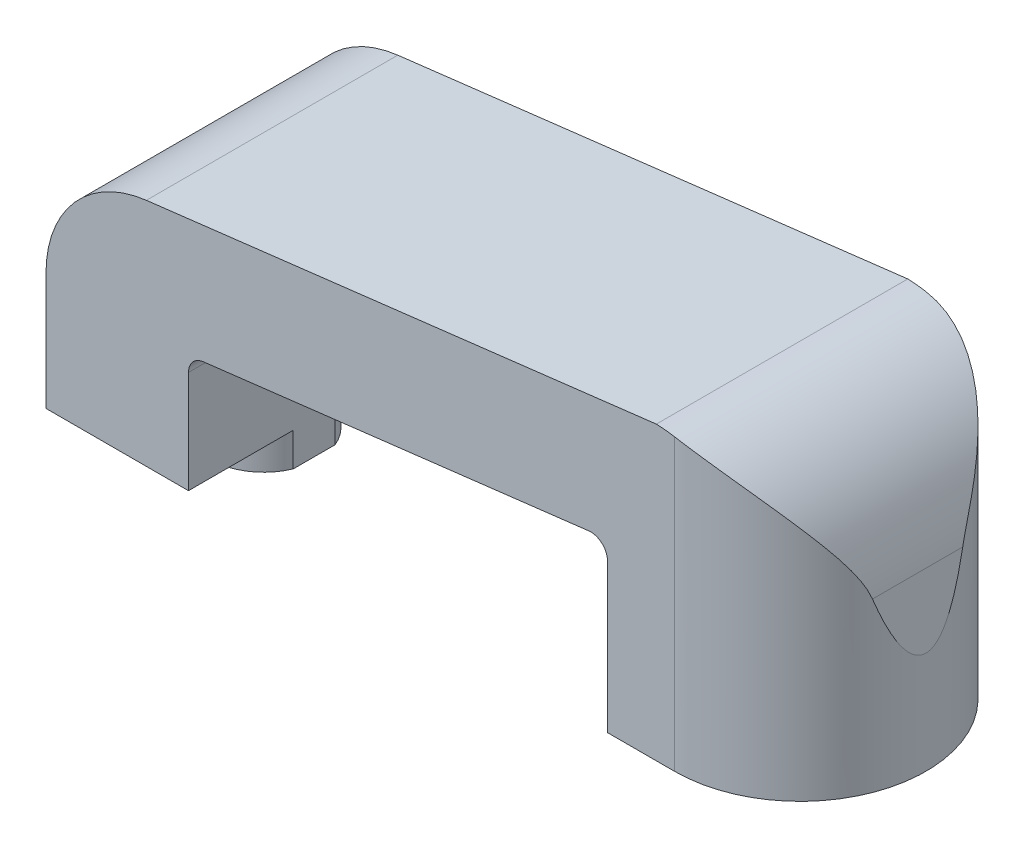
SolidWorks part; units mm, degrees
ref_plane "Ön Düzlem" through (0, 0, 0) normal (0, 0, 1) x (1, 0, 0)
ref_plane "Üst Düzlem" through (0, 0, 0) normal (0, 1, 0) x (1, 0, 0)
ref_plane "Sağ Düzlem" through (0, 0, 0) normal (1, 0, 0) x (0, 0, -1)
sketch "Sketch3" plane through (0, 0, 0) normal (0, 0, 1) x (1, 0, 0)
  line L0 (31.7681, 33.5206) -> (31.7681, 0) construction
  line L1 (0, 0) -> (-8.5, 0)
  line L2 (0, 0) -> (0, 6.1128)
  line L3 (0, 7) -> (-8.5, 7)
  line L4 (-8.5, 0) -> (-8.5, 7)
  line L5 (0.8809, 7.1057) -> (23.8809, 9.8657)
  line L6 (25, 0) -> (36, 0)
  line L7 (25, 0) -> (25, 8.8728)
  line L8 (25, 10) -> (36, 10)
  line L9 (36, 0) -> (36, 10)
  line L10 (-8.5, 0) -> (41.9166, 0) construction
  line L11 (-2.5127, 13.7487) -> (27.9143, 17.3999)
  arc A0 (-2.5127, 13.7487) -> (-8.5, 7) centre (-1.7029, 7) ccw
  arc A1 (27.9143, 17.3999) -> (36, 10) centre (27.5799, 8.9171) cw
  arc A2 (23.8809, 9.8657) -> (25, 8.8728) centre (24, 8.8728) cw
  arc A3 (0.8809, 7.1057) -> (0, 6.1128) centre (1, 6.1128) ccw
  point P15 (27.0903, 16.0845)
  point P17 (24.5808, 15.9874)
  point P18 (24.5808, 15.9874)
  point P25 (24.5808, 15.9874)
  point P26 (24.5808, 15.9874)
  point P27 (24.5808, 15.9874)
  point P28 (29.5444, 16.1291)
  point P29 (25, 17.08)
  dimension "D7" = 1
  dimension "D1" = 8.5
  dimension "D2" = 11
  dimension "D3" = 25
  dimension "D4" = 7
  dimension "D5" = 10
  dimension "D6" = 7
extrude "Boss-Extrude2" add sketch "Sketch3" along normal blind 15 contours A3 L5 A2 L7 L6 L9 A1 L11 A0 L4 L1 L2 region at (15.4185, 9.2084, 0)
sketch "Sketch4" plane through (0, 0, 0) normal (0, -1, 0) x (1, 0, 0)
  line L0 (25, 15) -> (25, 0) construction
  line L1 (29, 7.5) -> (29, 17.5654) construction
  line L2 (29, 7.5) -> (29, -2.3263) construction
  line L3 (25, 15) -> (36, 15) construction
  line L4 (25, 0) -> (36, 0) construction
  line L5 (36, 15) -> (36, 0) construction
  line L6 (29, 15) -> (36, 15)
  line L7 (29, 15) -> (29, 0)
  line L8 (29, 0) -> (36, 0)
  line L10 (36, 15) -> (36, 0)
  circle A0 centre (29, 7.5) radius 1.8409
  arc A1 (29, 15) -> (29, 0) centre (29, 7.5) cw
  point P5 (29, 15)
  point P6 (29, 0)
  line M5 (25, 0) -> (36, 0)
  line M6 (36, 0) -> (36, 15)
  line M7 (36, 15) -> (25, 15)
  dimension "D1" = 4
extrude "Cut-Extrude1" cut sketch "Sketch4" against normal blind 25 contours A1 M7 M6 | A1 M6 M5 region at (34.3801, 0, 13.6969) region at (34.3801, 0, 1.3031)
sketch "Sketch5" plane through (0, 0, 0) normal (0, -1, 0) x (1, 0, 0)
  line L0 (29, 15) -> (29, 0) construction
  line L1 (29, 15) -> (36, 15) construction
  line L2 (36, 15) -> (36, 0) construction
  line L3 (29, 0) -> (36, 0) construction
  line L4 (29, 15) -> (29, 0)
  line L5 (29, 15) -> (36, 15)
  line L6 (36, 15) -> (36, 0)
  line L7 (29, 0) -> (36, 0)
  arc A0 (29, 0) -> (29, 15) centre (29, 7.5) ccw construction
  circle A1 centre (29, 7.5) radius 1.8409
  circle A2 centre (29, 7.5) radius 1.8409
  arc A3 (29, 0) -> (29, 15) centre (29, 7.5) ccw
  line M6 (36, 4.8074) -> (36, 10.1926)
  dimension "D1" = 0
extrude "Boss-Extrude3" add sketch "Sketch5" against normal up to vertex contours A3 M6 region at (36.2006, 0, 7.5) up to point (36, 10, 10.1926)
sketch "Sketch6" plane through (0, 0, 15) normal (0, 0, 1) x (1, 0, 0)
  line L0 (-2.5127, 13.7487) -> (27.9143, 17.3999) construction
  line L1 (-2.5127, 13.7487) -> (27.8328, 17.3902)
  line L2 (36, 10) -> (36.5995, 5.3385)
  line L3 (36.5, 0) -> (36.5, 10)
  line L4 (36, 10) -> (36.5, 10)
  arc A0 (36, 10) -> (29, 17.2869) centre (27.5799, 8.9171) ccw construction
  arc A1 (29, 17.2869) -> (27.9143, 17.3999) centre (27.5799, 8.9171) ccw construction
  arc A2 (36, 10) -> (29, 17.2869) centre (27.5799, 8.9171) ccw
  arc A3 (29, 17.2869) -> (28.0016, 17.396) centre (27.5799, 8.9171) ccw
  arc A4 (28.0016, 17.396) -> (27.8328, 17.3902) centre (27.952, 16.3973) ccw
  dimension "D1" = 1
extrude "Cut-Extrude2" cut sketch "Sketch6" against normal blind 15 contours L4 L2 L3 region at (36.3333, 8.7041, 15)
sketch "Sketch7" plane through (0, 0, 0) normal (0, -1, 0) x (1, 0, 0)
  line L1 (25, 15) -> (25, 0) construction
  line L2 (25, 7.5) -> (40.587, 7.5) construction
  line L3 (29, 15) -> (29, 1.7627) construction
  line L4 (0, 8.75) -> (0, 6.25)
  line L7 (0, 7.5) -> (-12.8971, 7.5) construction
  circle A0 centre (-3, 7.5) radius 1.25
  circle A1 centre (29, 7.5) radius 1.25
  arc A2 (0, 8.75) -> (0, 6.25) centre (-3, 7.5) ccw
  circle A3 centre (29, 7.5) radius 3.25
  dimension "D2" = 2.5
  dimension "D3" = 6.5
  dimension "D1" = 32
extrude "Boss-Extrude4" add sketch "Sketch7" along normal blind 2 contours L4 A2 | A3 | A0 | A1
sketch "Sketch9" plane through (0, -2, 0) normal (0, -1, 0) x (1, 0, 0)
  line L1 (0, 6.25) -> (0, 8.75)
  line L2 (0, 6.25) -> (0, 8.75)
  circle A1 centre (29, 7.5) radius 3.25
  circle A2 centre (29, 7.5) radius 3.25
  circle A3 centre (29, 7.5) radius 1.25
  circle A4 centre (29, 7.5) radius 1.25
  circle A5 centre (-3, 7.5) radius 1.25
  circle A6 centre (-3, 7.5) radius 1.25
  arc A7 (0, 8.75) -> (0, 6.25) centre (-3, 7.5) ccw
  arc A8 (0, 8.75) -> (0, 6.25) centre (-3, 7.5) ccw
  point P11 (0, 0)
  circle M8 centre (-3, 7.5) radius 1.25
  dimension "D1" = 0
  dimension "D2" = 0
  dimension "D3" = 0
  dimension "D4" = 0
extrude "Cut-Extrude3" cut sketch "Sketch9" against normal blind 10 contours M8 | A4 | A6 region at (29, -2, 7.5) region at (-3, -2, 7.5)
sketch "Sketch10" plane through (0, 8, 0) normal (0, -1, 0) x (1, 0, 0)
  circle A1 centre (29, 7.5) radius 1.25
  circle A2 centre (29, 7.5) radius 1.25
  dimension "D1" = 0
extrude "Cut-Extrude4" cut sketch "Sketch10" against normal blind 1.5
